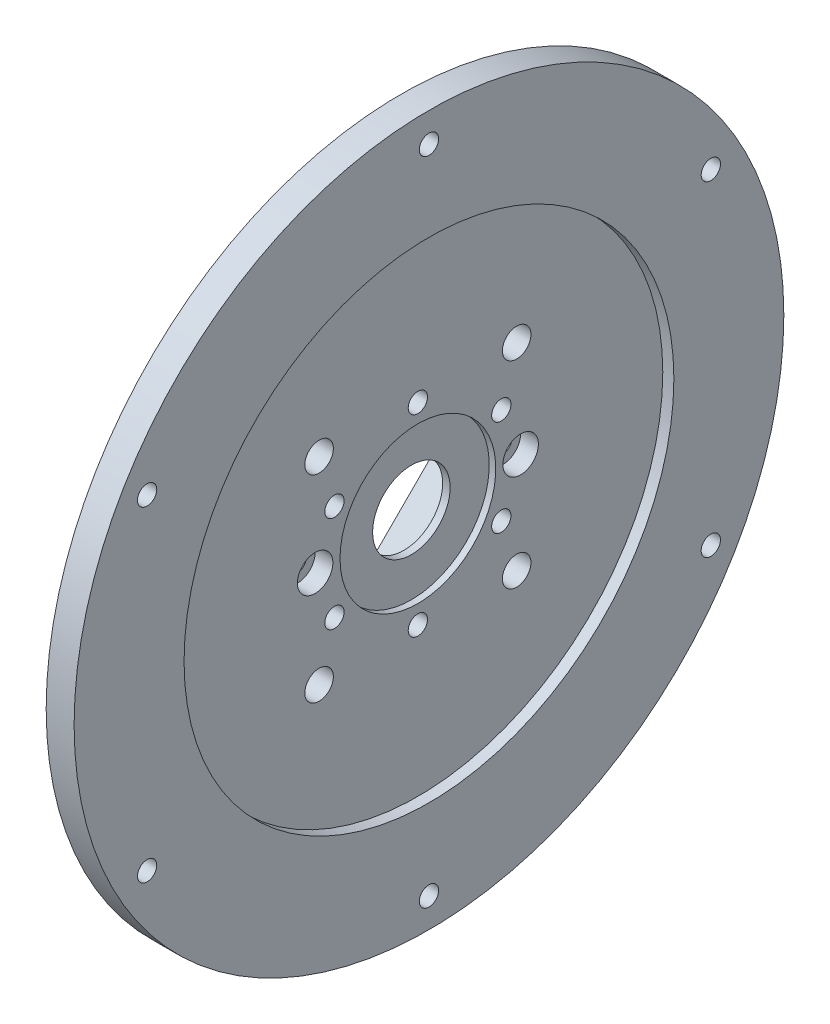
SolidWorks part; units mm, degrees
ref_plane "Front Plane" through (0, 0, 0) normal (0, 0, 1) x (1, 0, 0)
ref_plane "Top Plane" through (0, 0, 0) normal (0, 1, 0) x (1, 0, 0)
ref_plane "Right Plane" through (0, 0, 0) normal (1, 0, 0) x (0, 0, -1)
sketch "Sketch1" plane through (0, 0, 0) normal (0, 0, 1) x (1, 0, 0)
  line L0 (0, 0) -> (58.591, 0) construction
  line L2 (0, 0) -> (18.4, 0)
  line L3 (0, 0) -> (0, 2.5)
  line L4 (0, 2.5) -> (18.4, 2.5)
  line L5 (18.4, 0) -> (18.4, 2.5)
  line L6 (6.0094, 2.5) -> (6.0094, 6)
  line L11 (6.0094, 6) -> (9.9794, 6)
  line L16 (12.9794, 6) -> (12.9794, 3)
  line L17 (12.9794, 3) -> (13.6398, 3)
  line L18 (13.6398, 3) -> (13.6398, 2.5)
  line L19 (13.6398, 2.5) -> (6.0094, 2.5)
  line L22 (13.6398, 2.5) -> (16.1198, 2.5)
  line L23 (13.6398, 2.5) -> (13.6398, 4)
  line L24 (13.6398, 4) -> (16.1198, 4)
  line L25 (16.1198, 2.5) -> (16.1198, 4)
  line L27 (6.0094, 6) -> (9.9794, 6)
  line L28 (6.0094, 6) -> (6.0094, 9)
  line L29 (6.0094, 9) -> (9.9794, 9)
  line L30 (9.9794, 6) -> (9.9794, 9)
  line L31 (6.0094, 9) -> (6.0094, 8.25)
  line L32 (6.0094, 8.25) -> (5.0094, 8.25)
  line L33 (8.6609, 22.001) -> (8.6609, 12.476) construction
  line L34 (5.0094, 12.476) -> (12.3124, 12.476)
  line L35 (9.9794, 9) -> (12.3124, 9)
  line L36 (5.0094, 7.9375) -> (1.8344, 7.9375)
  line L37 (5.0094, 8.25) -> (5.0094, 12.476)
  line L38 (5.0094, 7.9375) -> (5.0094, 13.9365)
  line L39 (5.0094, 13.9365) -> (1.8344, 13.9365)
  line L40 (1.8344, 7.9375) -> (1.8344, 13.9365)
  line L41 (5.0094, 22.001) -> (12.3124, 22.001)
  line L42 (5.0094, 22.001) -> (5.0094, 30.1625)
  line L43 (5.0094, 30.1625) -> (12.3124, 30.1625)
  line L44 (12.3124, 22.001) -> (12.3124, 30.1625)
  line L49 (16.6398, 22.001) -> (16.6398, 7.5)
  line L51 (23.0198, 7.5) -> (23.0198, 6.5)
  line L54 (16.1198, 4) -> (13.6398, 4)
  line L56 (18.0398, 7.5) -> (23.0198, 7.5)
  line L57 (13.3124, 22.001) -> (16.6398, 22.001)
  line L58 (16.1198, 3.5) -> (20.0198, 3.5)
  line L59 (29.9098, 14) -> (26.9098, 11)
  line L60 (4.0094, 31.75) -> (18.0398, 31.75)
  line L61 (18.0398, 7.5) -> (23.0198, 7.5)
  line L62 (18.0398, 7.5) -> (18.0398, 12)
  line L63 (18.0398, 12) -> (23.0198, 12)
  line L64 (23.0198, 7.5) -> (23.0198, 12)
  line L65 (18.0398, 31.75) -> (18.0398, 12)
  line L66 (23.0198, 11) -> (26.9098, 11)
  line L67 (34.8098, 23) -> (31.3098, 19.5)
  line L68 (35.8098, 31) -> (38.7998, 33.99)
  line L69 (29.9098, 14) -> (29.9098, 15)
  line L70 (29.9098, 15) -> (22.9398, 15)
  line L71 (22.9398, 15) -> (21.0398, 15)
  line L72 (18.0398, 7.5) -> (16.6398, 7.5)
  line L73 (21.0398, 15) -> (21.0398, 43)
  line L74 (19.5798, 40) -> (9.6198, 40)
  line L75 (9.6198, 40) -> (4.0094, 40)
  line L76 (21.0398, 43) -> (19.5798, 43)
  line L77 (22.9398, 15) -> (29.9098, 15)
  line L78 (22.9398, 15) -> (22.9398, 21)
  line L79 (22.9398, 21) -> (29.9098, 21)
  line L80 (29.9098, 15) -> (29.9098, 21)
  line L81 (9.6198, 40) -> (19.5798, 40)
  line L82 (9.6198, 40) -> (9.6198, 50)
  line L83 (9.6198, 50) -> (19.5798, 50)
  line L84 (19.5798, 40) -> (19.5798, 50)
  line L85 (4.0094, 40) -> (4.0094, 31.75)
  line L86 (12.9794, 3) -> (12.9794, 2.5)
  line L87 (31.3098, 19.5) -> (29.9098, 19.5)
  line L88 (21.4694, 63.5) -> (21.4694, 51.308)
  line L89 (21.4694, 63.5) -> (25.9398, 63.5)
  line L90 (25.9398, 63.5) -> (25.9398, 25)
  line L91 (27.8398, 25) -> (25.9398, 25)
  line L92 (9.6198, 48) -> (8.1598, 48)
  line L93 (8.1598, 48) -> (8.1598, 53.476)
  line L94 (8.1598, 53.476) -> (19.5798, 53.476)
  line L95 (19.5798, 53.476) -> (19.5798, 50)
  line L96 (13.8698, 63.001) -> (13.8698, 53.476) construction
  line L97 (8.1598, 63.001) -> (19.5798, 63.001)
  line L98 (8.1598, 63.001) -> (8.1598, 68.2625)
  line L99 (8.1598, 68.2625) -> (19.5798, 68.2625)
  line L100 (19.5798, 63.001) -> (19.5798, 68.2625)
  line L101 (12.9794, 6) -> (11.9794, 6)
  line L102 (8.1598, 44.825) -> (4.9848, 44.825)
  line L103 (8.1598, 44.825) -> (8.1598, 54.9365)
  line L104 (8.1598, 54.9365) -> (4.9848, 54.9365)
  line L106 (9.9794, 6) -> (10.8794, 6)
  line L107 (27.8398, 25) -> (34.8098, 25)
  line L108 (34.8098, 25) -> (34.8098, 23)
  line L109 (0, 0) -> (-2, 0)
  line L110 (0, 0) -> (0, 11)
  line L111 (27.8398, 25) -> (34.8098, 25)
  line L112 (27.8398, 25) -> (27.8398, 32.5)
  line L113 (27.8398, 32.5) -> (34.8098, 32.5)
  line L114 (34.8098, 25) -> (34.8098, 32.5)
  line L115 (35.8098, 31) -> (34.8098, 31)
  line L116 (27.8398, 32.5) -> (27.8398, 64.5)
  line L117 (20.5373, 74.025) -> (6.2023, 74.025)
  line L118 (6.2023, 74.025) -> (6.2023, 76.2)
  line L119 (38.7998, 47.29) -> (30.8398, 55.25)
  line L120 (0, 11) -> (-2, 11)
  line L121 (38.7998, 43.815) -> (30.8623, 43.815)
  line L123 (-4.8152, 69.85) -> (1.5348, 76.2)
  line L124 (38.7998, 47.29) -> (38.7998, 33.99)
  line L125 (-2, 0) -> (-2, 11)
  line L126 (38.7998, 37.465) -> (30.8623, 37.465)
  line L127 (30.8623, 43.815) -> (30.8623, 37.465)
  line L128 (6.0094, 2.5) -> (6.0094, 0)
  line L129 (-0.0152, 63.5) -> (-0.0152, 30)
  line L132 (4.9848, 63.5) -> (-0.0152, 63.5)
  line L136 (-1.8152, 30) -> (-11.7752, 30)
  line L138 (-13.7752, 25.4) -> (-2, 25.4)
  line L139 (-2, 25.4) -> (-2, 11.5)
  line L140 (27.8398, 64.5) -> (20.5373, 64.5)
  line L141 (-1.8152, 30) -> (-11.7752, 30)
  line L142 (-1.8152, 30) -> (-1.8152, 39)
  line L143 (-1.8152, 39) -> (-11.7752, 39)
  line L144 (-11.7752, 30) -> (-11.7752, 39)
  line L145 (20.5373, 64.5) -> (20.5373, 74.025)
  line L146 (-12.7752, 37) -> (-12.7752, 47.29)
  line L147 (-12.7752, 37) -> (-11.7752, 37)
  line L148 (30.8398, 55.25) -> (30.8398, 76.2)
  line L149 (11.9794, 6) -> (11.9794, 5.45)
  line L154 (-2, 11.5) -> (0.5, 11.5)
  line L155 (4.9848, 60.6197) -> (24.0348, 60.6197)
  line L160 (4.9848, 60.6197) -> (4.9848, 55.8572)
  line L161 (4.9848, 55.8572) -> (24.0348, 55.8572)
  line L166 (24.0348, 60.6197) -> (24.0348, 55.8572)
  line L167 (4.9848, 60.6197) -> (24.0348, 55.8572) construction
  line L172 (4.9848, 55.8572) -> (24.0348, 60.6197) construction
  line L173 (24.0348, 62.2072) -> (25.9398, 62.2072)
  line L174 (11.9794, 5.45) -> (10.8794, 5.45)
  line L175 (10.8794, 6) -> (10.8794, 5.45)
  line L176 (24.0348, 62.2072) -> (24.0348, 54.2697)
  line L177 (24.0348, 54.2697) -> (25.9398, 54.2697)
  line L178 (25.9398, 62.2072) -> (25.9398, 54.2697)
  line L179 (24.0348, 62.2072) -> (25.9398, 54.2697) construction
  line L180 (24.0348, 54.2697) -> (25.9398, 62.2072) construction
  line L181 (3, 19.6197) -> (15.7, 19.6197)
  line L182 (3, 19.6197) -> (3, 14.8572)
  line L183 (3, 14.8572) -> (15.7, 14.8572)
  line L184 (15.7, 19.6197) -> (15.7, 14.8572)
  line L185 (3, 19.6197) -> (15.7, 14.8572) construction
  line L186 (3, 14.8572) -> (15.7, 19.6197) construction
  line L187 (15.7, 21.2072) -> (16.6398, 21.2072)
  line L188 (15.7, 21.2072) -> (15.7, 13.2697)
  line L189 (15.7, 13.2697) -> (16.6398, 13.2697)
  line L190 (16.6398, 21.2072) -> (16.6398, 13.2697)
  line L191 (15.7, 21.2072) -> (16.6398, 13.2697) construction
  line L192 (15.7, 13.2697) -> (16.6398, 21.2072) construction
  line L193 (0.5, 11.5) -> (0.5, 6.9375)
  line L194 (0.5, 6.9375) -> (1.8344, 6.9375)
  line L195 (23.0198, 6.5) -> (20.0198, 3.5)
  line L196 (4.9848, 63.5) -> (4.9848, 54.9365)
  line L197 (3, 43.825) -> (4.9848, 43.825)
  line L198 (1.8344, 6.9375) -> (1.8344, 7.9375)
  line L199 (6.0094, 0) -> (12.9794, 0)
  line L200 (12.9794, 0) -> (12.9794, 2.5)
  line L201 (18.0398, 31.75) -> (18.0398, 35.875)
  line L202 (18.0398, 35.875) -> (21.0398, 35.875)
  line L203 (30.8398, 76.2) -> (6.2023, 76.2)
  line L204 (2.7573, 69.85) -> (7.2023, 69.85) construction
  line L205 (7.2023, 67.4688) -> (26.2523, 67.4688)
  line L206 (7.2023, 74.025) -> (7.2023, 64.5)
  line L207 (7.2023, 64.5) -> (-1.8152, 64.5)
  line L208 (-1.8152, 64.5) -> (-1.8152, 39)
  line L209 (-12.7752, 47.29) -> (-4.8152, 55.25)
  line L210 (-4.8152, 55.25) -> (-4.8152, 69.85)
  line L211 (7.2023, 67.4688) -> (7.2023, 72.2312)
  line L212 (7.2023, 72.2312) -> (26.2523, 72.2313)
  line L213 (26.2523, 67.4688) -> (26.2523, 72.2313)
  line L214 (26.2523, 73.8187) -> (30.8398, 73.8187)
  line L215 (26.2523, 73.8187) -> (26.2523, 65.8813)
  line L216 (26.2523, 65.8813) -> (30.8398, 65.8813)
  line L217 (30.8398, 73.8187) -> (30.8398, 65.8813)
  line L218 (2.7573, 72.2313) -> (24.9823, 72.2313)
  line L219 (2.7573, 72.2313) -> (2.7573, 67.4687)
  line L220 (2.7573, 67.4687) -> (24.9823, 67.4687)
  line L221 (24.9823, 72.2313) -> (24.9823, 67.4687)
  line L222 (24.9823, 69.85) -> (20.5373, 69.85) construction
  line L223 (21.4694, 51.308) -> (22.9398, 51.308)
  line L224 (22.9398, 51.308) -> (22.9398, 21)
  line L225 (13.6398, 4) -> (13.6398, 12.2697)
  line L226 (13.6398, 12.2697) -> (13.3124, 12.2697)
  line L227 (13.3124, 12.2697) -> (13.3124, 22.001)
  line L228 (12.3124, 9) -> (12.3124, 12.476)
  line L229 (-1.8152, 30) -> (-0.0152, 30)
  line L230 (8.1598, 65.6317) -> (2.7573, 65.6317) construction
  line L231 (19.5798, 65.6317) -> (24.9823, 65.6317) construction
  line L232 (1.5348, 76.2) -> (6.2023, 76.2)
  line L233 (-11.7752, 30) -> (-13.7752, 30)
  line L234 (-13.7752, 30) -> (-13.7752, 25.4)
  line L235 (3, 13.9365) -> (3, 43.825)
  line L236 (4.9848, 54.9365) -> (4.9848, 44.825)
  line L237 (4.9848, 43.825) -> (4.9848, 44.825)
  circle A0 centre (26.8898, 25.95) radius 0.95
  circle A1 centre (21.9898, 15.95) radius 0.95
  circle A2 centre (17.3398, 8.2) radius 0.7
  circle A3 centre (10.4294, 6.45) radius 0.45
  circle A4 centre (-0.9152, 30.9) radius 0.9
  point P7 (24.9873, 58.2385)
  point P131 (16.1699, 17.2385)
  point P135 (14.5098, 58.2385)
  point P146 (9.35, 17.2385)
sketch "Sketch2" plane through (0, 0, 0) normal (0, 0, 1) x (1, 0, 0)
  line L0 (-1.8152, 30) -> (-11.7752, 30) construction
  line L1 (-2, 25.4) -> (-2, 11.5) construction
  line L3 (-13.7752, 25.4) -> (-2, 25.4) construction
  line L4 (-2, 11.5) -> (0.5, 11.5) construction
  line L5 (0.5, 11.5) -> (0.5, 6.9375) construction
  line L6 (0.5, 6.9375) -> (1.8344, 6.9375) construction
  line L10 (4.9848, 63.5) -> (-0.0152, 63.5) construction
  line L11 (-0.0152, 63.5) -> (-0.0152, 30) construction
  line L14 (-1.8152, 30) -> (-11.7752, 30)
  line L15 (-2, 25.4) -> (-2, 11.5)
  line L17 (-13.7752, 25.4) -> (-2, 25.4)
  line L18 (-2, 11.5) -> (0.5, 11.5)
  line L19 (0.5, 11.5) -> (0.5, 6.9375)
  line L20 (0.5, 6.9375) -> (1.8344, 6.9375)
  line L24 (4.9848, 63.5) -> (-0.0152, 63.5)
  line L25 (-0.0152, 63.5) -> (-0.0152, 30)
  line L28 (-1.8152, 30) -> (-0.0152, 30) construction
  line L29 (-1.8152, 30) -> (-0.0152, 30)
  line L30 (-13.7752, 30) -> (-13.7752, 25.4) construction
  line L31 (-11.7752, 30) -> (-13.7752, 30) construction
  line L32 (-13.7752, 30) -> (-13.7752, 25.4)
  line L33 (-11.7752, 30) -> (-13.7752, 30)
  line L34 (1.8344, 6.9375) -> (1.8344, 7.9375) construction
  line L35 (1.8344, 7.9375) -> (1.8344, 13.9365) construction
  line L36 (5.0094, 13.9365) -> (1.8344, 13.9365) construction
  line L37 (3, 13.9365) -> (3, 43.825) construction
  line L40 (4.9848, 63.5) -> (4.9848, 54.9365) construction
  line L41 (1.8344, 6.9375) -> (1.8344, 7.9375)
  line L42 (1.8344, 7.9375) -> (1.8344, 13.9365)
  line L43 (3, 13.9365) -> (1.8344, 13.9365)
  line L44 (3, 13.9365) -> (3, 43.825)
  line L47 (4.9848, 63.5) -> (4.9848, 54.9365)
  line L48 (4.9848, 43.825) -> (4.9848, 44.825) construction
  line L49 (3, 43.825) -> (4.9848, 43.825) construction
  line L50 (4.9848, 54.9365) -> (4.9848, 44.825) construction
  line L51 (4.9848, 43.825) -> (4.9848, 44.825)
  line L52 (3, 43.825) -> (4.9848, 43.825)
  line L53 (4.9848, 54.9365) -> (4.9848, 44.825)
revolve "Revolve1" add sketch "Sketch2" angle 360 about L0 region at (-0.9152, 29.4041, 0)
sketch "Sketch3" plane through (0, 0, 0) normal (1, 0, 0) x (0, 0, -1)
  line L0 (0, 0) -> (0, 69.85) construction
  line L1 (0, 0) -> (13.6271, 68.5079) construction
  line L2 (0, 0) -> (0, 58.2385) construction
  line L3 (0, 0) -> (50.436, 29.1192) construction
  line L4 (0, 0) -> (0, 31.75) construction
  line L5 (0, 0) -> (12.1502, 29.3332) construction
  line L6 (0, 0) -> (0, 17.2385) construction
  line L7 (0, 0) -> (14.929, 8.6192) construction
  line L8 (0, 0) -> (0, 58.2385) construction
  line L9 (0, 0) -> (50.436, 29.1192) construction
  line L10 (0, 0) -> (5.9583, 29.9542) construction
  line L11 (0, 0) -> (16.9677, 25.394) construction
  circle A0 centre (0, 0) radius 69.85 construction
  circle A1 centre (0, 0) radius 58.2385 construction
  circle A2 centre (0, 0) radius 31.75 construction
  circle A3 centre (0, 0) radius 17.2385 construction
  circle A4 centre (0, 69.85) radius 3.175
  circle A5 centre (0, 58.2385) radius 4.7625
  circle A6 centre (0, 31.75) radius 3.175
  circle A7 centre (0, 17.2385) radius 4.7625
  circle A8 centre (13.6271, 68.5079) radius 3.175
  circle A9 centre (26.7304, 64.533) radius 3.175
  circle A10 centre (38.8066, 58.0782) radius 3.175
  circle A11 centre (49.3914, 49.3914) radius 3.175
  circle A12 centre (58.0782, 38.8066) radius 3.175
  circle A13 centre (64.533, 26.7304) radius 3.175
  circle A14 centre (68.5079, 13.6271) radius 3.175
  circle A15 centre (69.85, 0) radius 3.175
  circle A16 centre (68.5079, -13.6271) radius 3.175
  circle A17 centre (64.533, -26.7304) radius 3.175
  circle A18 centre (58.0782, -38.8066) radius 3.175
  circle A19 centre (49.3914, -49.3914) radius 3.175
  circle A20 centre (38.8066, -58.0782) radius 3.175
  circle A21 centre (26.7304, -64.533) radius 3.175
  circle A22 centre (13.6271, -68.5079) radius 3.175
  circle A23 centre (0, -69.85) radius 3.175
  circle A24 centre (-13.6271, -68.5079) radius 3.175
  circle A25 centre (-26.7304, -64.533) radius 3.175
  circle A26 centre (-38.8066, -58.0782) radius 3.175
  circle A27 centre (-49.3914, -49.3914) radius 3.175
  circle A28 centre (-58.0782, -38.8066) radius 3.175
  circle A29 centre (-64.533, -26.7304) radius 3.175
  circle A30 centre (-68.5079, -13.6271) radius 3.175
  circle A31 centre (-69.85, 0) radius 3.175
  circle A32 centre (-68.5079, 13.6271) radius 3.175
  circle A33 centre (-64.533, 26.7304) radius 3.175
  circle A34 centre (-58.0782, 38.8066) radius 3.175
  circle A35 centre (-49.3914, 49.3914) radius 3.175
  circle A36 centre (-38.8066, 58.0782) radius 3.175
  circle A37 centre (-26.7304, 64.533) radius 3.175
  circle A38 centre (-13.6271, 68.5079) radius 3.175
  circle A47 centre (50.436, 29.1192) radius 4.7625
  circle A48 centre (50.436, -29.1192) radius 4.7625
  circle A49 centre (0, -58.2385) radius 4.7625
  circle A50 centre (-50.436, -29.1192) radius 4.7625
  circle A51 centre (-50.436, 29.1192) radius 4.7625
  circle A58 centre (12.1502, 29.3332) radius 3.175
  circle A59 centre (22.4506, 22.4506) radius 3.175
  circle A60 centre (29.3332, 12.1502) radius 3.175
  circle A61 centre (31.75, 0) radius 3.175
  circle A62 centre (29.3332, -12.1502) radius 3.175
  circle A63 centre (22.4506, -22.4506) radius 3.175
  circle A64 centre (12.1502, -29.3332) radius 3.175
  circle A65 centre (0, -31.75) radius 3.175
  circle A66 centre (-12.1502, -29.3332) radius 3.175
  circle A67 centre (-22.4506, -22.4506) radius 3.175
  circle A68 centre (-29.3332, -12.1502) radius 3.175
  circle A69 centre (-31.75, 0) radius 3.175
  circle A70 centre (-29.3332, 12.1502) radius 3.175
  circle A71 centre (-22.4506, 22.4506) radius 3.175
  circle A72 centre (14.929, 8.6192) radius 4.7625
  circle A73 centre (14.929, -8.6192) radius 4.7625
  circle A74 centre (0, -17.2385) radius 4.7625
  circle A75 centre (-14.929, -8.6192) radius 4.7625
  circle A76 centre (-14.929, 8.6192) radius 4.7625
  circle A77 centre (0, 0) radius 50
  circle A78 centre (0, 0) radius 9
  circle A79 centre (-12.1502, 29.3332) radius 3.175
  circle A80 centre (0, 0) radius 76.2
  circle A81 centre (0, 0) radius 74.025
  circle A82 centre (0, 69.85) radius 3.9687
  circle A83 centre (49.3914, 49.3914) radius 3.9687
  circle A84 centre (69.85, 0) radius 3.9688
  circle A85 centre (49.3914, -49.3914) radius 3.9687
  circle A86 centre (0, -69.85) radius 3.9687
  circle A87 centre (-49.3914, -49.3914) radius 3.9687
  circle A88 centre (-69.85, 0) radius 3.9688
  circle A89 centre (-49.3914, 49.3914) radius 3.9687
  circle A90 centre (0, 69.85) radius 2.3812
  circle A91 centre (13.6271, 68.5079) radius 2.3812
  circle A92 centre (26.7304, 64.533) radius 2.3813
  circle A93 centre (38.8066, 58.0782) radius 2.3812
  circle A94 centre (49.3914, 49.3914) radius 2.3812
  circle A95 centre (58.0782, 38.8066) radius 2.3812
  circle A96 centre (64.533, 26.7304) radius 2.3813
  circle A97 centre (68.5079, 13.6271) radius 2.3813
  circle A98 centre (69.85, 0) radius 2.3813
  circle A99 centre (68.5079, -13.6271) radius 2.3813
  circle A100 centre (64.533, -26.7304) radius 2.3813
  circle A101 centre (58.0782, -38.8066) radius 2.3812
  circle A102 centre (49.3914, -49.3914) radius 2.3812
  circle A103 centre (38.8066, -58.0782) radius 2.3812
  circle A104 centre (26.7304, -64.533) radius 2.3813
  circle A105 centre (13.6271, -68.5079) radius 2.3812
  circle A106 centre (0, -69.85) radius 2.3812
  circle A107 centre (-13.6271, -68.5079) radius 2.3812
  circle A108 centre (-26.7304, -64.533) radius 2.3813
  circle A109 centre (-38.8066, -58.0782) radius 2.3812
  circle A110 centre (-49.3914, -49.3914) radius 2.3812
  circle A111 centre (-58.0782, -38.8066) radius 2.3812
  circle A112 centre (-64.533, -26.7304) radius 2.3812
  arc A113 (3.0399, 30.8338) -> (8.9911, 29.65) centre (5.9583, 29.9542) cw
  arc A114 (14.6081, 27.3234) -> (19.6532, 23.9523) centre (16.9677, 25.394) cw
  arc A115 (23.9523, 19.6532) -> (27.3234, 14.6081) centre (25.394, 16.9677) cw
  arc A116 (29.65, 8.9911) -> (30.8338, 3.0399) centre (29.9542, 5.9583) cw
  arc A117 (30.8338, -3.0399) -> (29.65, -8.9911) centre (29.9542, -5.9583) cw
  arc A118 (27.3234, -14.6081) -> (23.9523, -19.6532) centre (25.394, -16.9677) cw
  arc A119 (19.6532, -23.9523) -> (14.6081, -27.3234) centre (16.9677, -25.394) cw
  arc A120 (8.9911, -29.65) -> (3.0399, -30.8338) centre (5.9583, -29.9542) cw
  arc A121 (-3.0399, -30.8338) -> (-8.9911, -29.65) centre (-5.9583, -29.9542) cw
  arc A122 (-14.6081, -27.3234) -> (-19.6532, -23.9523) centre (-16.9677, -25.394) cw
  arc A123 (-23.9523, -19.6532) -> (-27.3234, -14.6081) centre (-25.394, -16.9677) cw
  arc A124 (-29.65, -8.9911) -> (-30.8338, -3.0399) centre (-29.9542, -5.9583) cw
  arc A125 (-30.8338, 3.0399) -> (-29.65, 8.9911) centre (-29.9542, 5.9583) cw
  arc A126 (-27.3234, 14.6081) -> (-23.9523, 19.6532) centre (-25.394, 16.9677) cw
  arc A127 (-19.6532, 23.9523) -> (-14.6081, 27.3234) centre (-16.9677, 25.394) cw
  arc A128 (-8.9911, 29.65) -> (-3.0399, 30.8338) centre (-5.9583, 29.9542) cw
  arc A129 (26.9875, 0) -> (26.9932, 0.1932) centre (30.2705, 0) cw
  arc A130 (65.0988, 0.2771) -> (65.0875, 0) centre (68.4964, 0) ccw
  circle A131 centre (1.5875, 0) radius 40
  circle A132 centre (1.5875, 0) radius 2.5
  circle A133 centre (1.5875, 0) radius 3
  circle A134 centre (1.5875, 0) radius 43
  circle A135 centre (-68.5079, -13.6271) radius 2.3813
  circle A136 centre (-69.85, 0) radius 2.3813
  circle A137 centre (-68.5079, 13.6271) radius 2.3813
  circle A138 centre (-64.533, 26.7304) radius 2.3812
  circle A139 centre (-58.0782, 38.8066) radius 2.3812
  circle A140 centre (-49.3914, 49.3914) radius 2.3812
  circle A141 centre (-38.8066, 58.0782) radius 2.3812
  circle A142 centre (-26.7304, 64.533) radius 2.3813
  circle A143 centre (-13.6271, 68.5079) radius 2.3812
  circle A144 centre (0, 58.2385) radius 2.3812
  circle A145 centre (0, 58.2385) radius 3.9688
  circle A146 centre (50.436, 29.1192) radius 3.9688
  circle A147 centre (50.436, 29.1192) radius 2.3813
  circle A148 centre (50.436, -29.1192) radius 3.9687
  circle A149 centre (50.436, -29.1192) radius 2.3812
  circle A150 centre (0, -58.2385) radius 3.9687
  circle A151 centre (0, -58.2385) radius 2.3812
  circle A152 centre (-50.436, -29.1192) radius 3.9687
  circle A153 centre (-50.436, -29.1192) radius 2.3812
  circle A154 centre (-50.436, 29.1192) radius 3.9687
  circle A155 centre (-50.436, 29.1192) radius 2.3812
  spline S1 degree 4 number of poles 499 (26.9875, 0) -> (26.9932, 0.1932)
  spline S3 degree 4 number of poles 617 (65.0875, 0) -> (65.0988, 0.2771)
  point P116 (0, 0)
  point P225 (0, 0)
sketch "Sketch4" plane through (0, 0, 0) normal (1, 0, 0) x (0, 0, -1)
  circle A0 centre (-14.929, -8.6192) radius 4.7625 construction
  circle A1 centre (-14.929, 8.6192) radius 4.7625 construction
  circle A2 centre (0, 17.2385) radius 4.7625 construction
  circle A3 centre (14.929, 8.6192) radius 4.7625 construction
  circle A4 centre (14.929, -8.6192) radius 4.7625 construction
  circle A5 centre (0, -17.2385) radius 4.7625 construction
  circle A6 centre (0, -58.2385) radius 4.7625 construction
  circle A7 centre (-50.436, -29.1192) radius 4.7625 construction
  circle A8 centre (50.436, -29.1192) radius 4.7625 construction
  circle A9 centre (50.436, 29.1192) radius 4.7625 construction
  circle A10 centre (0, 58.2385) radius 4.7625 construction
  circle A11 centre (-50.436, 29.1192) radius 4.7625 construction
  circle A12 centre (-14.929, -8.6192) radius 4.7625
  circle A13 centre (-14.929, 8.6192) radius 4.7625
  circle A14 centre (0, 17.2385) radius 4.7625
  circle A15 centre (14.929, 8.6192) radius 4.7625
  circle A16 centre (14.929, -8.6192) radius 4.7625
  circle A17 centre (0, -17.2385) radius 4.7625
  circle A18 centre (0, -58.2385) radius 4.7625
  circle A19 centre (-50.436, -29.1192) radius 4.7625
  circle A20 centre (50.436, -29.1192) radius 4.7625
  circle A21 centre (50.436, 29.1192) radius 4.7625
  circle A22 centre (0, 58.2385) radius 4.7625
  circle A23 centre (-50.436, 29.1192) radius 4.7625
  circle A24 centre (0, 58.2385) radius 1.7272
  circle A25 centre (50.436, 29.1192) radius 1.7272
  circle A26 centre (50.436, -29.1192) radius 1.7272
  circle A27 centre (0, -58.2385) radius 1.7272
  circle A28 centre (-50.436, -29.1192) radius 1.7272
  circle A29 centre (-50.436, 29.1192) radius 1.7272
  circle A30 centre (-14.929, 8.6192) radius 1.7272
  circle A31 centre (0, 17.2385) radius 1.7272
  circle A32 centre (14.929, 8.6192) radius 1.7272
  circle A33 centre (14.929, -8.6192) radius 1.7272
  circle A34 centre (0, -17.2385) radius 1.7272
  circle A35 centre (-14.929, -8.6192) radius 1.7272
  dimension "D1" = 3.4544
extrude "Cut-Extrude1" cut sketch "Sketch4" against normal through all and the other way through all contours A29 | A30 | A31 | A32 | A33 | A34 | A35 | A25 | A26 | A24 | A28 | A27
sketch "Sketch5" plane through (3, 0, 0) normal (1, 0, 0) x (0, 0, -1)
  line L0 (-18.385, 0) -> (0, 0) construction
  line L1 (0, 0) -> (18.385, 0) construction
  circle A0 centre (-18.385, 0) radius 1.5875
  circle A1 centre (18.385, 0) radius 1.5875
  dimension "D2" = 3.175
  dimension "D1" = 36.77
extrude "Cut-Extrude2" cut sketch "Sketch5" against normal through all
sketch "Sketch6" plane through (3, 0, 0) normal (1, 0, 0) x (0, 0, -1)
  circle A0 centre (-18.385, 0) radius 3.175
  circle A1 centre (18.385, 0) radius 3.175
  dimension "D1" = 6.35
extrude "Cut-Extrude3" cut sketch "Sketch6" against normal blind 3.175
sketch "Sketch7" plane through (-13.7752, 0, 0) normal (-1, 0, 0) x (0, 0, 1)
  line L0 (3.0706, 25.2137) -> (25.2137, 3.0706)
  line L1 (25.2137, -3.0706) -> (3.0706, -25.2137)
  line L2 (-3.0706, -25.2137) -> (-25.2137, -3.0706)
  line L3 (-25.2137, 3.0706) -> (-3.0706, 25.2137)
  circle A3 centre (0, 0) radius 25.4 construction
  circle A4 centre (0, 0) radius 25.4
  point P15 (0, 0)
  circle M5 centre (0, 0) radius 25.4
  dimension "D2" = 40
  dimension "D1" = 4
extrude "Boss-Extrude1" add sketch "Sketch7" against normal up to next contours L0 M5 | L3 M5 | L2 M5 | L1 M5 region at (-13.7752, 15.6843, 15.6843) region at (-13.7752, 15.6843, -15.6843) region at (-13.7752, -15.6843, 15.6843) region at (-13.7752, -15.6843, -15.6843)
fillet "Fillet1" radius 3.175 8 edges at (-7.8876, -25.2137, -3.0706) (-7.8876, -25.2137, 3.0706) (-7.8876, -3.0706, 25.2137) (-7.8876, 3.0706, 25.2137) (-7.8876, -3.0706, -25.2137) (-7.8876, 3.0706, -25.2137) (-7.8876, 25.2137, 3.0706) (-7.8876, 25.2137, -3.0706)
sketch "Sketch8" plane through (-13.7752, 0, 0) normal (-1, 0, 0) x (0, 0, 1)
  line L0 (0, 0) -> (17.6777, 17.6777) construction
  line L1 (0, 0) -> (13.9248, 0) construction
  line L2 (17.6777, 17.6777) -> (21.2132, 21.2132) construction
  line L3 (17.6777, 17.6777) -> (14.1421, 14.1421) construction
  line L7 (3.874, 24.4103) -> (24.4103, 3.874) construction
  circle A0 centre (17.6777, 17.6777) radius 2.5527
  circle A1 centre (0, 0) radius 30 construction
  circle A2 centre (17.6777, -17.6777) radius 2.5527
  circle A3 centre (-17.6777, -17.6777) radius 2.5527
  circle A4 centre (-17.6777, 17.6777) radius 2.5527
  point P20 (0, 0)
  dimension "D2" = 5.1054
  dimension "D1" = 45
  dimension "D3" = 4
extrude "Cut-Extrude4" cut sketch "Sketch8" against normal through all
